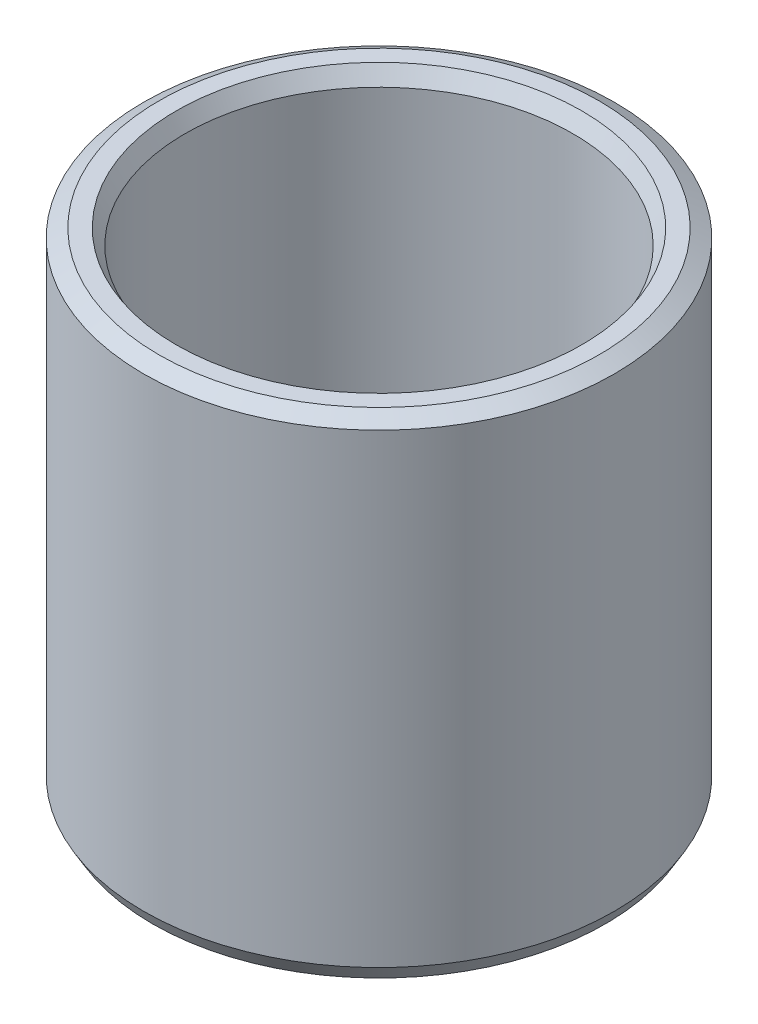
SolidWorks part; units mm, degrees
ref_plane "Front Plane" through (0, 0, 0) normal (0, 0, 1) x (1, 0, 0)
ref_plane "Top Plane" through (0, 0, 0) normal (0, 1, 0) x (1, 0, 0)
ref_plane "Right Plane" through (0, 0, 0) normal (1, 0, 0) x (0, 0, -1)
sketch "Sketch1" plane through (0, 0, 0) normal (0, 1, 0) x (1, 0, 0)
  circle A0 centre (0, 0) radius 37.5
  dimension "SLEEVE_OD" = 75
extrude "Boss-Extrude1" add sketch "Sketch1" along normal blind 77.9991
sketch "Sketch2" plane through (0, 0, 0) normal (0, 1, 0) x (1, 0, 0)
  circle A0 centre (0, 0) radius 30.8933
  dimension "BORE_D" = 61.7866
extrude "Cut-Extrude1" cut sketch "Sketch2" along normal through all
chamfer "Chamfer1" distance 1.4103 angle 60 4 edges at (0, 77.9991, 30.8933) (0, 0, 30.8933) (0, 0, 37.5) (0, 77.9991, 37.5) first distance on face at (0, 77.9991, 30.8933) first distance on face at (0, 0, 30.8933) first distance on face at (0, 77.9991, 37.5)
